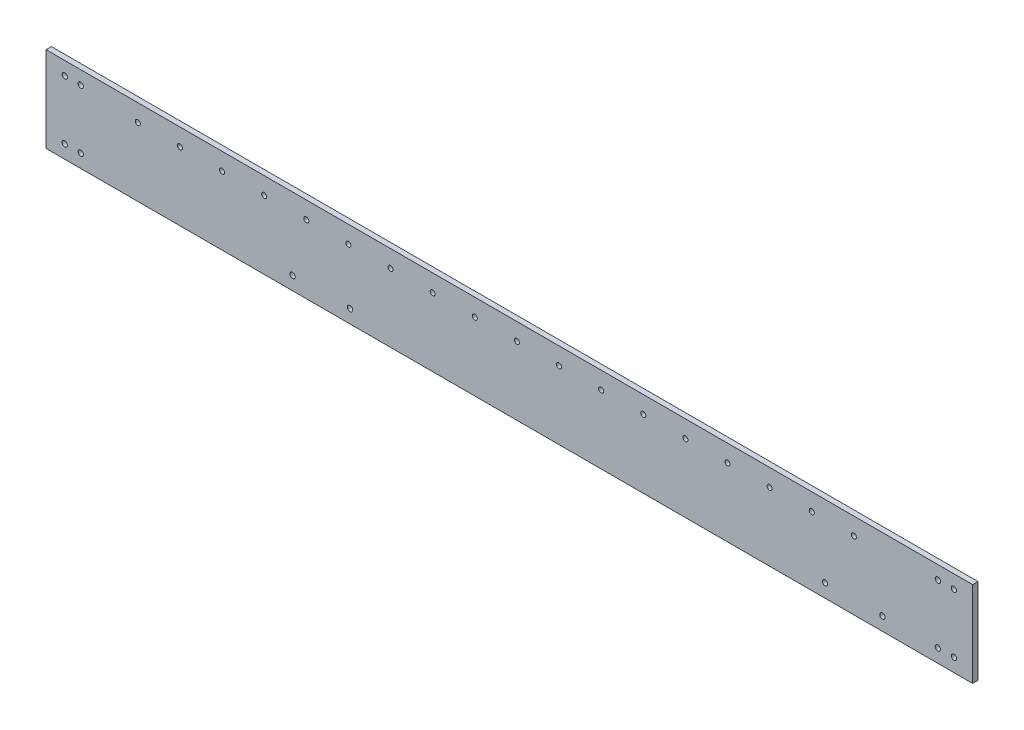
SolidWorks part; units mm, degrees
ref_plane "Front Plane" through (0, 0, 0) normal (0, 0, 1) x (1, 0, 0)
ref_plane "Top Plane" through (0, 0, 0) normal (0, 1, 0) x (1, 0, 0)
ref_plane "Right Plane" through (0, 0, 0) normal (1, 0, 0) x (0, 0, -1)
sketch "Sketch1" plane through (0, 0, 0) normal (1, 0, 0) x (0, 0, -1)
  line L0 (0, 0) -> (-3.175, 0)
  line L3 (-3.175, 0) -> (-3.175, 50.8)
  line L4 (-3.175, 50.8) -> (0, 50.8)
  line L5 (0, 50.8) -> (0, 0)
  dimension "LHeight" = 50.8
  dimension "LMaterialThickness" = 3.175
extrude "Boss-Extrude1" add sketch "Sketch1" along normal blind 550
sketch "SideHoles-Sketch4" plane through (0, 0, 3.175) normal (0, 0, 1) x (1, 0, 0)
  line L1 (550, 50.8) -> (550, 0) construction
  line L2 (0, 50.8) -> (0, 0) construction
  line L3 (550, 50.8) -> (0, 50.8) construction
  line L4 (550, 0) -> (0, 0) construction
  line L5 (550, 50.8) -> (0, 50.8) construction
  line L6 (0, 50.8) -> (0, 0) construction
  line L7 (550, 50.8) -> (550, 0) construction
  circle A1 centre (11.1125, 42.8625) radius 1.5875
  circle A3 centre (529.3625, 42.8625) radius 1.5875
  circle A4 centre (20.6375, 42.8625) radius 1.5875
  circle A5 centre (538.8875, 42.8625) radius 1.5875
  circle A6 centre (11.1125, 7.9375) radius 1.5875
  circle A7 centre (20.6375, 7.9375) radius 1.5875
  circle A8 centre (529.3625, 7.9375) radius 1.5875
  circle A9 centre (538.8875, 7.9375) radius 1.5875
  circle A10 centre (54.5, 40.575) radius 1.5
  circle A11 centre (79.5, 40.575) radius 1.5
  circle A12 centre (104.5, 40.575) radius 1.5
  circle A13 centre (129.5, 40.575) radius 1.5
  circle A14 centre (154.5, 40.575) radius 1.5
  circle A15 centre (179.5, 40.575) radius 1.5
  circle A16 centre (204.5, 40.575) radius 1.5
  circle A17 centre (229.5, 40.575) radius 1.5
  circle A18 centre (254.5, 40.575) radius 1.5
  circle A19 centre (279.5, 40.575) radius 1.5
  circle A20 centre (304.5, 40.575) radius 1.5
  circle A21 centre (329.5, 40.575) radius 1.5
  circle A22 centre (354.5, 40.575) radius 1.5
  circle A23 centre (379.5, 40.575) radius 1.5
  circle A24 centre (496.4875, 7.9375) radius 1.5875
  circle A26 centre (180.4875, 7.9375) radius 1.5875
  circle A29 centre (404.5, 40.575) radius 1.5
  circle A30 centre (429.5, 40.575) radius 1.5
  circle A31 centre (454.5, 40.575) radius 1.5
  circle A32 centre (479.5, 40.575) radius 1.5
  circle A34 centre (146.3625, 7.9375) radius 1.5875
  circle A36 centre (462.3625, 7.9375) radius 1.5875
  dimension "D2" = 3.175
  dimension "D10" = 3
  dimension "D14" = 3.175
  dimension "D4" = 7.9375
  dimension "D3" = 11.1125
  dimension "D5" = 20.6375
  dimension "D1" = 11.1125
  dimension "D6" = 20.6375
  dimension "D7" = 7.9375
  dimension "D9" = 10.225
  dimension "D8" = 54.5
  dimension "D12" = 25
  dimension "D15" = 7.9375
  dimension "D17" = 53.5125
  dimension "D18" = 316
  dimension "D13" = 34.125
  dimension "D16" = 34.125
  dimension "D11" = 18
extrude "SideHoles-Cut-Extrude3" cut sketch "SideHoles-Sketch4" against normal through all
equation "\"MidLeftOrRightSideRailHeight\"= 2.0in"
equation "\"RailThickness\"= .125in'Spec"
equation "\"SideRailHoleY1FromEdge\"= \"HoleOffsetFromEdge\""
equation "\"SideRailHoleX1FromSide\"= \"HoleOffsetFromSide\""
equation "\"MidSideRailLength\"= \"SideRailLength\""
equation "\"VSWidth\"= 1.25in'Spec"
equation "\"HoleOffsetFromEdge\"= \"RailThickness\" * 2.5"
equation "\"HoleOffsetFromSide\"= \"RailThickness\" * 3.5"
equation "\"SideRailHoleX2FromSide\"= \"VSWidth\" - \"HoleOffsetFromEdge\" - \"RailThickness\"'Equals 20.6375"
equation "\"FasteningHoleDiameter\"= .125in"
equation "\"StepperWidth\"= 42mm'Spec"
equation "\"D2@SideHoles-Sketch4\"=\"FasteningHoleDiameter\""
equation "\"LHeight@Sketch1\"=\"MidLeftOrRightSideRailHeight\""
equation "\"LMaterialThickness@Sketch1\"=\"RailThickness\""
equation "\"D1@Boss-Extrude1\"=\"MidSideRailLength\""
equation "\"D4@SideHoles-Sketch4\"=\"SideRailHoleY1FromEdge\""
equation "\"D3@SideHoles-Sketch4\"=\"SideRailHoleX1FromSide\" "
equation "\"D5@SideHoles-Sketch4\"=\"SideRailHoleX2FromSide\" "
equation "\"D1@SideHoles-Sketch4\"=\"SideRailHoleX1FromSide\" "
equation "\"D6@SideHoles-Sketch4\"=\"SideRailHoleX2FromSide\""
equation "\"LinearRailXMountHole\"= \"StepperWidth\" + \"LinearRailFirstHoleOffsetFromEdge\""
equation "\"D9@SideHoles-Sketch4\"=\"V6.3 GantryMiddleToToTopOfMidSideRail\""
equation "\"D8@SideHoles-Sketch4\"=\"LinearRailXMountHole\""
equation "\"LinearRailHoleDistance\"= 25mm'Spec"
equation "\"D12@SideHoles-Sketch4\"=\"LinearRailHoleDistance\""
equation "\"SideRailLength\"= 550mm"
equation "\"LinearRailFirstHoleOffsetFromEdge\"= 12.5mm'Spec"
equation "\"D7@SideHoles-Sketch4\"= \"MidRailRodStabilizerMountingHoleOffsetFromEdge\""
equation "\"DistanceFromBedFrontToFirstLeftStepperHole\"= \"LeadScrewNutPadSize\" + 10mm'Equals 34"
equation "\"BeltTensionerDepth\"= \"BeltTensionerBackWallThickness\" + \"BeltTensionerInnerDepth\"'Equals 23.4"
equation "\"20TGT2PulleyDiameter\"= 17.9mm'Spec"
equation "\"BeltTensionerSpaceBetweenPulleyAndWall\"= 1.5mm"
equation "\"BeltTensionerBackWallThickness\"= 4mm"
equation "\"BeltTensionerInnerDepth\"= \"20TGT2PulleyDiameter\" + \"BeltTensionerSpaceBetweenPulleyAndWall\""
equation "\"DistanceFromFrontSideToBedFront\"= \"RailThickness\" + \"BeltTensionerDepth\" + 10mm'Equals 36.575"
equation "\"DistanceBetweenFrontToBackStepperHoles\"= \"BedLength\" - \"DistanceFromBedFrontToFirstLeftStepperHole\"'Equals 316"
equation "\"BedLength\"= \"BedInnerSquareLength\" + \"BedLWidth\" * 2 - \"BedOverlap\" * 2 + \"BedIncreasedByLength\"'Equals 350"
equation "\"BedOverlap\"= 20mm"
equation "\"BedThirdSize\"= 70mm"
equation "\"BedInnerSquareWidth\"= \"BedThirdSize\" * 3'Equals 210"
equation "\"BedLWidth\"= \"BedThirdSize\" + \"BedOverlap\"'Equals 90"
equation "\"BedIncreasedByLength\"= 0mm"
equation "\"D14@SideHoles-Sketch4\"= \"FasteningHoleDiameter\""
equation "\"D15@SideHoles-Sketch4\"= \"HoleOffsetFromEdge\""
equation "\"BedInnerSquareLength\"= \"BedInnerSquareWidth\""
equation "\"GABMidWallHeight\"= 28mm'Must equal 28 or changes alignment"
equation "\"20TGT2PulleyWidth\"= 8.7mm'The STL of the Pulley in the diagram is a bit larger"
equation "\"GABMidShortRiserHeight\"= \"GABMidWallHeight\" / 2 - \"20TGT2PulleyWidth\"'Equals 5.3"
equation "\"GABUpperHeight\"= 6mm"
equation "\"GABLowerHeight\"= 3mm"
equation "\"GABRiserBossOffset\"= 0.8mm'Aligns Pulleys"
equation "\"GABHeight\"= \"GABLowerHeight\" + \"GABMidWallHeight\" + \"GABUpperHeight\""
equation "\"StepperShaftLength\"= 24mm'Pulley will be attached to the end"
equation "\"V6.1 FromGantryPulleyToGantryMiddle\"= \"GABHeight\" / 2 - \"GABMidShortRiserHeight\" - \"GABLowerHeight\" + \"GABRiserBossOffset\" / 2"
equation "\"V6.2 GantryMiddleToTopOfMidBackRail\"= \"StepperShaftLength\" - \"V6.1 FromGantryPulleyToGantryMiddle\""
equation "\"V6.3 GantryMiddleToToTopOfMidSideRail\"= \"V6.2 GantryMiddleToTopOfMidBackRail\" - \"RailThickness\""
equation "\"DistanceFromFrontSideToFirstLeftStabilizerMountingHole\"= \"DistanceFromFrontSideToFirstLeftStepperHole\" - \"DistanceFromStepperHoleToRodStabilizerMountingHole\"'Equals 53.5125"
equation "\"DistanceFromFrontSideToFirstLeftStepperHole\"= \"DistanceFromFrontSideToBedFront\" + \"DistanceFromBedFrontToFirstLeftStepperHole\"'Equals 70.575"
equation "\"LeadScrewNutMountingHoleFlangeDiameter\"= 22mm'Spec"
equation "\"LeadScrewNutPadSize\"= \"LeadScrewNutMountingHoleFlangeDiameter\" + 2mm'Equals 24"
equation "\"D17@SideHoles-Sketch4\"=\"DistanceFromFrontSideToFirstLeftStabilizerMountingHole\""
equation "\"D18@SideHoles-Sketch4\"=\"DistanceBetweenFrontToBackStepperHoles\""
equation "\"MidRailRodStabilizerMountingHoleOffsetFromEdge\"= \"HoleOffsetFromEdge\""
equation "\"RodStabilizerLength\"= 50mm"
equation "\"DistanceFromStepperHoleToRodStabilizerMountingHole\"= \"RodStabilizerLength\" / 2 - \"HoleOffsetFromEdge\"'Equals 17.0625"
equation "\"D13@SideHoles-Sketch4\"=\"RodStabilizerLength\" - \"HoleOffsetFromEdge\" * 2"
equation "\"D16@SideHoles-Sketch4\"=\"RodStabilizerLength\" - \"HoleOffsetFromEdge\" *2"
